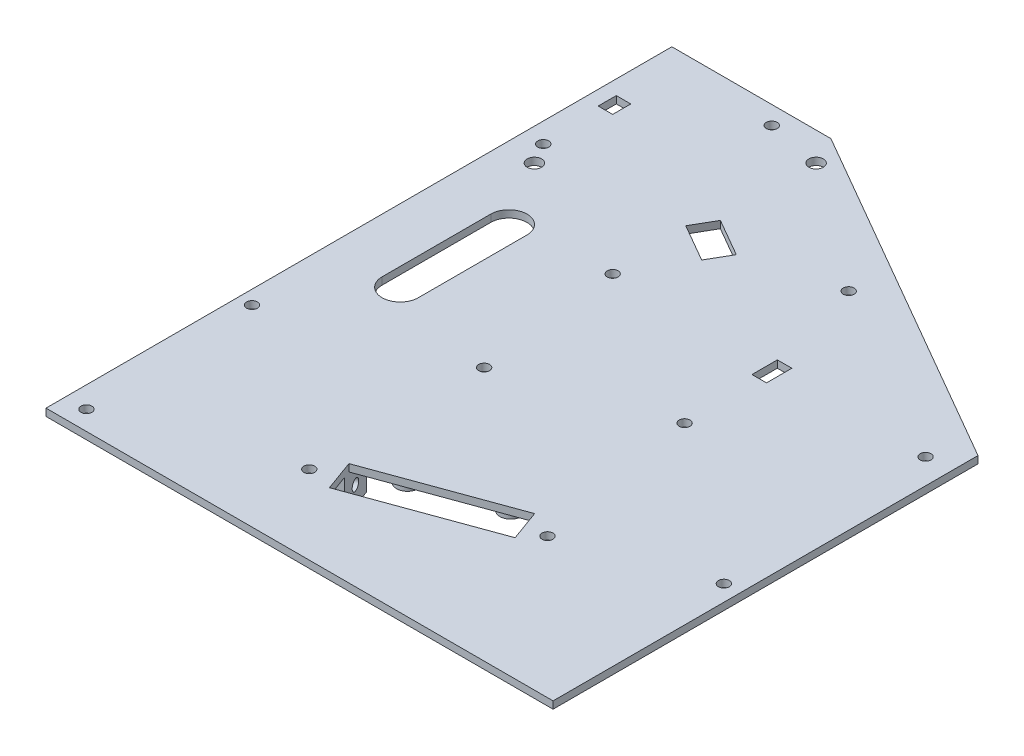
SolidWorks part; units mm, degrees
ref_plane "Front Plane" through (0, 0, 0) normal (0, 0, 1) x (1, 0, 0)
ref_plane "Top Plane" through (0, 0, 0) normal (0, 1, 0) x (1, 0, 0)
ref_plane "Right Plane" through (0, 0, 0) normal (1, 0, 0) x (0, 0, -1)
sketch "Sketch1" plane through (0, 0, 0) normal (0, 1, 0) x (1, 0, 0)
  line L1 (-70, 100) -> (70, 100)
  line L2 (-70, 100) -> (-70, -100)
  line L3 (-70, -100) -> (70, -100)
  line L4 (70, 100) -> (70, -100)
  line L5 (-70, 100) -> (70, -100) construction
  line L6 (-70, -100) -> (70, 100) construction
  point P0 (0, 0)
  dimension "D1" = 200
  dimension "D2" = 140
extrude "Boss-Extrude1" add sketch "Sketch1" along normal blind 2
sketch "Sketch2" plane through (0, 2, 0) normal (0, 1, 0) x (1, 0, 0)
  line L0 (-60, 63) -> (30, 11.0385) construction
  line L1 (-70, 100) -> (-70, -100) construction
  line L2 (70, -14.4027) -> (23.0154, -31.5037) construction
  line L3 (70, -100) -> (70, 100) construction
  line L4 (-50.6218, 98) -> (-70, 98) construction
  line L5 (-60, 63) -> (-50.6218, 63) construction
  line L6 (70, 100) -> (-70, 100) construction
  line L7 (70, -14.4027) -> (47.7176, -14.4027) construction
  line L8 (-51.25, 78.1554) -> (38.75, 26.1939) construction
  line L9 (-60, 63) -> (-70, 63) construction
  line L10 (-50.6218, 98) -> (70, 28.359) construction
  line L11 (-25.2872, 59.1244) -> (-21.7872, 65.1865)
  line L12 (-25.2872, 59.1244) -> (-14.8949, 53.1244)
  line L13 (-21.7872, 65.1865) -> (-11.3949, 59.1865)
  line L14 (-14.8949, 53.1244) -> (-11.3949, 59.1865)
  line L15 (-25.2872, 59.1244) -> (-11.3949, 59.1865)
  line L16 (-51.25, 78.1554) -> (-70, 78.1554) construction
  line L17 (-50.6218, 98) -> (47.5, 41.3494) construction
  line L18 (-66, 80.6554) -> (-62, 80.6554)
  line L19 (-66, 80.6554) -> (-66, 75.6554)
  line L20 (-66, 75.6554) -> (-62, 75.6554)
  line L21 (-62, 80.6554) -> (-62, 75.6554)
  line L22 (-66, 80.6554) -> (-62, 75.6554) construction
  line L23 (-66, 75.6554) -> (-62, 80.6554) construction
  line L24 (19.4272, 32.69) -> (23.4317, 32.69)
  line L25 (19.4272, 32.69) -> (19.4272, 39.6978)
  line L26 (19.4272, 39.6978) -> (23.4317, 39.6978)
  line L27 (23.4317, 32.69) -> (23.4317, 39.6978)
  line L28 (19.4272, 32.69) -> (23.4317, 39.6978) construction
  line L29 (19.4272, 39.6978) -> (23.4317, 32.69) construction
  line L30 (30, 11.0385) -> (30, -28.9615) construction
  line L31 (-70, -65.3585) -> (-14.5723, -45.1845) construction
  line L32 (30, 11.0385) -> (-70, -25.3585) construction
  circle A0 centre (-41.7237, 72.6554) radius 20
  point P10 (-18.341, 59.1554)
  point P13 (-64, 78.1554)
  point P25 (-64, 75.6554)
  point P26 (21.4295, 36.1939)
  dimension "D6" = 40
  dimension "D1" = 37
  dimension "D2" = 30
  dimension "D3" = 20
  dimension "D4" = 40
  dimension "D5" = 10
  dimension "D9" = 11
  dimension "D10" = 5
  dimension "D11" = 4
  dimension "D12" = 4
  dimension "D13" = 12
  dimension "D14" = 7
  dimension "D15" = 20
  dimension "D16" = 40
  dimension "D17" = 50
  dimension "D18" = 40
  dimension "D19" = 21
  dimension "D7" = 35
  dimension "D8" = 17.5
sketch "Sketch3" plane through (0, 2, 0) normal (0, 1, 0) x (1, 0, 0)
  line L0 (-50.6218, 98) -> (70, 28.359) construction
  line L1 (-60, 63) -> (30, 11.0385) construction
  line L2 (30, 11.0385) -> (-70, -25.3585) construction
  line L3 (70, -14.4027) -> (23.0154, -31.5037) construction
  line L4 (-70, -65.3585) -> (-14.5723, -45.1845) construction
  line L5 (-50.6218, 98) -> (70, 28.359)
  line L6 (-60, 63) -> (30, 11.0385)
  line L7 (30, 11.0385) -> (-70, -25.3585)
  line L8 (70, -14.4027) -> (23.0154, -31.5037)
  line L9 (-70, -65.3585) -> (-14.5723, -45.1845)
  line L10 (-60, 63) -> (-70, 63) construction
  line L11 (-60, 63) -> (-70, 63)
extrude "Cut-Extrude-Thin1" [suppressed] cut sketch "Sketch3" against normal blind 0.5 thin contours L11 L6 L7 thin type one direction wall 2.5
sketch "Sketch4" plane through (0, 0, 0) normal (0, -1, 0) x (1, 0, 0)
  circle A0 centre (-41.7237, -72.6554) radius 20 construction
  circle A1 centre (-41.7237, -72.6554) radius 20
extrude "Cut-Extrude1" cut sketch "Sketch4" against normal blind 1
sketch "Sketch6" plane through (0, 0, 0) normal (0, -1, 0) x (1, 0, 0)
  line L0 (-22.2783, -92.1009) -> (-61.1692, -53.21) construction
  line L1 (-23.6925, -93.5151) -> (-62.5834, -54.6242) construction
  line L2 (-20.8641, -90.6867) -> (-59.7549, -51.7958) construction
  line L4 (-51.25, -78.1554) -> (38.75, -26.1939) construction
  arc A0 (-23.6925, -93.5151) -> (-20.8641, -90.6867) centre (-22.2783, -92.1009) ccw construction
  arc A1 (-59.7549, -51.7958) -> (-62.5834, -54.6242) centre (-61.1692, -53.21) ccw construction
  circle A2 centre (-61.1692, -53.21) radius 2
  circle A3 centre (-22.2783, -92.1009) radius 2
  point P2 (-41.7237, -72.6554)
  dimension "D1" = 55
  dimension "D2" = 4
  dimension "D3" = 105
extrude "Cut-Extrude2" cut sketch "Sketch6" against normal up to next
extrude "Cut-Extrude4" cut sketch "Sketch2" against normal through all and the other way through all contours L15 L12 L14 | L11 L15 L13 | L21 L18 L19 L20 | L24 L27 L26 L25 region at (-17.1923, 2, -57.1451) region at (-19.4898, 2, -61.1658) region at (-64, 2, -78.1554) region at (21.4295, 2, -36.1939)
sketch "Sketch7" plane through (0, 2, 0) normal (0, 1, 0) x (1, 0, 0)
  line L0 (-14.5723, -45.1845) -> (23.0154, -31.5037)
  line L1 (23.0154, -31.5037) -> (25.7515, -39.0213)
  line L2 (25.7515, -39.0213) -> (-11.8362, -52.7021)
  line L3 (-11.8362, -52.7021) -> (-14.5723, -45.1845)
  line L4 (-14.5723, -45.1845) -> (23.0154, -31.5037)
  line L5 (-14.5723, -45.1845) -> (-14.9144, -44.2448)
  line L6 (23.0154, -31.5037) -> (22.6733, -30.564)
  line L7 (-14.9144, -44.2448) -> (22.6733, -30.564)
  line L8 (70, -14.4027) -> (23.0154, -31.5037) construction
  dimension "D1" = 8
  dimension "D2" = 40
  dimension "D3" = 1
extrude "Cut-Extrude5" cut sketch "Sketch7" against normal up to surface (2 mm away) contours L3 L2 L1 L0 | L7 L5 L0 L6 region at (4.0505, 2, 37.8743) region at (5.5896, 2, 42.1029) up to face at (21.4295, 0, -36.1939)
sketch "Sketch8" plane through (10.198, 0, -3.7118) normal (-0.9397, 0, 0.342) x (0.342, 0, 0.9397)
  line L1 (38.4755, 0) -> (28.4755, 0)
  line L2 (38.4755, 0) -> (38.4755, -10)
  line L3 (38.4755, -10) -> (28.4755, -10)
  line L4 (28.4755, 0) -> (28.4755, -10)
  line L5 (-96.9966, 0) -> (-92.2981, 0) construction
  circle A0 centre (33.4755, -5) radius 1.5
  point P9 (28.4755, -5)
  point P11 (33.4755, -10)
  dimension "D3" = 3
  dimension "D1" = 10
  dimension "D2" = 10
  dimension "D4" = 2
extrude "Boss-Extrude2" add sketch "Sketch8" against normal blind 4
ref_plane "Plane1" through (-8.5959, 0, 3.1286) normal (-0.9397, 0, 0.342) x (0.342, 0, 0.9397)
mirror "Mirror1" about plane through (-8.5959, 0, 3.1286) normal (-0.9397, 0, 0.342) of "Boss-Extrude2"
sketch "Sketch9" plane through (0, 0, 0) normal (0, -1, 0) x (-1, 0, 0)
  line L5 (15.4671, -16.7774) -> (9.3107, -33.6919) construction
  line L6 (16.4068, -17.1194) -> (10.2504, -34.0339)
  line L7 (14.5274, -16.4354) -> (8.3711, -33.3498)
  line L8 (-22.6733, -30.564) -> (14.9144, -44.2448) construction
  line L9 (17.6505, -36.7273) -> (14.2303, -46.1242) construction
  line L10 (18.2862, -17.8035) -> (12.1298, -34.7179)
  line L11 (12.648, -15.7513) -> (6.4917, -32.6658)
  arc A0 (16.4068, -17.1194) -> (14.5274, -16.4354) centre (15.4671, -16.7774) ccw
  arc A1 (8.3711, -33.3498) -> (10.2504, -34.0339) centre (9.3107, -33.6919) ccw
  arc A2 (6.4917, -32.6658) -> (12.1298, -34.7179) centre (9.3107, -33.6919) ccw
  arc A3 (18.2862, -17.8035) -> (12.648, -15.7513) centre (15.4671, -16.7774) ccw
  point P7 (12.3889, -25.2346)
  dimension "D5" = 1
  dimension "D1" = 8
  dimension "D2" = 7.875
  dimension "D3" = 2
  dimension "D7" = 18
extrude "Boss-Extrude4" add sketch "Sketch9" along normal blind 5
mirror "Mirror2" about plane through (-8.5959, 0, 3.1286) normal (-0.9397, 0, 0.342) of "Boss-Extrude4"
sketch "Sketch10" plane through (0, 0, 0) normal (0, -1, 0) x (1, 0, 0)
  line L0 (-28.8362, -55.9772) -> (-26.2381, -54.4772)
  line L1 (-28.8362, -55.9772) -> (-31.5862, -51.2141)
  line L2 (-26.2381, -54.4772) -> (-28.9881, -49.7141)
  line L3 (-31.5862, -51.2141) -> (-28.9881, -49.7141)
  line L4 (-25.2872, -59.1244) -> (-14.8949, -53.1244) construction
  line L6 (-25.2872, -59.1244) -> (-21.7872, -65.1865) construction
  dimension "D1" = 4.5
  dimension "D2" = 5.5
  dimension "D3" = 3
  dimension "D4" = 1.5
extrude "Boss-Extrude5" add sketch "Sketch10" along normal blind 23
sketch "Sketch11" plane through (-45.866, 0, -26.4808) normal (-0.866, 0, -0.5) x (-0.5, 0, 0.866)
  line L0 (-31.5596, -20.0043) -> (-31.5596, -16.0043) construction
  line L1 (-32.5596, -20.0043) -> (-32.5596, -16.0043)
  line L2 (-30.5596, -20.0043) -> (-30.5596, -16.0043)
  line L3 (-28.5596, -23) -> (-34.0596, -23) construction
  line L4 (-28.5596, -23) -> (-28.5596, 0) construction
  line L5 (-31.5596, -6.5043) -> (-31.5596, -2.5043) construction
  line L6 (-32.5596, -6.5043) -> (-32.5596, -2.5043)
  line L7 (-30.5596, -6.5043) -> (-30.5596, -2.5043)
  arc A0 (-32.5596, -20.0043) -> (-30.5596, -20.0043) centre (-31.5596, -20.0043) ccw
  arc A1 (-30.5596, -16.0043) -> (-32.5596, -16.0043) centre (-31.5596, -16.0043) ccw
  arc A2 (-32.5596, -6.5043) -> (-30.5596, -6.5043) centre (-31.5596, -6.5043) ccw
  arc A3 (-30.5596, -2.5043) -> (-32.5596, -2.5043) centre (-31.5596, -2.5043) ccw
  point P3 (-31.5596, -18.0043)
  point P19 (-31.5596, -4.5043)
  dimension "D1" = 2.9957
  dimension "D2" = 4
  dimension "D3" = 3
  dimension "D4" = 2
  dimension "D5" = 13.5
extrude "Cut-Extrude6" cut sketch "Sketch11" against normal up to next
ref_plane "Plane2" through (21.0298, 0, -36.4247) normal (-0.5, 0, 0.866) x (0.866, 0, 0.5)
mirror "Mirror3" about plane through (21.0298, 0, -36.4247) normal (-0.5, 0, 0.866) of "Cut-Extrude6", "Boss-Extrude5"
hole_wizard "Ø3.0mm Clearance Dowel Hole1" positions "Sketch14" profile "Sketch15" hole size "Ø3.0" standard "ANSI Metric" end condition through all
sketch "Sketch14" plane through (-89.742, 2, 119.4997) normal (0, 1, 0) x (1, 0, 0)
  point P0 (23.5423, 99.781)
  point P1 (25.5944, 52.0145)
  point P2 (70.6996, 68.4315)
  point P3 (70.5269, 116.8821)
  point P4 (111.4918, 131.26)
  point P5 (119.5864, 85.3143)
  point P6 (155.2948, 98.311)
  point P7 (152.8064, 156.4818)
  point P8 (65.8782, 157.0177)
  point P9 (102.577, 185.4818)
  point P10 (52.3475, 214.4818)
  point P11 (25.242, 178.4997)
sketch "Sketch15" plane through (-66.1998, 2, 19.7187) normal (1, 0, 0) x (0, 0, 1)
  line L0 (0, 0) -> (0, 25)
  line L1 (0, 25) -> (1.5, 25)
  line L2 (1.5, 25) -> (1.5, 0)
  line L3 (1.5, 0) -> (0, 0)
  line L4 (0, -6.35) -> (0, 107.95) construction
  dimension "Thru Hole Dia." = 3
  dimension "Thru Hole Depth" = 25
sketch "Sketch16" plane through (0, 2, 0) normal (0, 1, 0) x (1, 0, 0)
  line L1 (-43.6218, 110.1244) -> (83.0261, 110.1244)
  line L2 (-43.6218, 110.1244) -> (77, 40.4833)
  line L3 (-43.6218, 110.1244) -> (77, 40.4833)
  line L4 (83.0261, 110.1244) -> (83.0261, 36.9032)
  line L5 (83.0261, 36.9032) -> (77, 40.4833)
  dimension "D1" = 14
extrude "Cut-Extrude7" cut sketch "Sketch16" against normal through all
sketch "Sketch17" plane through (0, 2, 0) normal (0, 1, 0) x (1, 0, 0)
  line L0 (-43.2303, 98) -> (-26.6218, 98)
  line L1 (-26.6218, 98) -> (68, 43.3701)
  line L2 (68, 43.3701) -> (68, 33.0364)
  line L3 (70, -100) -> (70, 44.5248) construction
  line L4 (-26.0859, 100) -> (70, 44.5248) construction
  line L5 (-26.0859, 100) -> (-70, 100) construction
  line L6 (-43.2303, 98) -> (-46.6944, 100)
  line L7 (-46.6944, 100) -> (-26.0859, 100)
  line L8 (-26.0859, 100) -> (70, 44.5248)
  line L9 (70, 44.5248) -> (70, 31.875)
  line L10 (70, 31.875) -> (68, 33.0364)
  dimension "D1" = 2
  dimension "D2" = 2
  dimension "D3" = 2
extrude "Boss-Extrude6" [suppressed] add sketch "Sketch17" along normal blind 4
sketch "Sketch18" plane through (0, 2, 0) normal (0, 1, 0) x (1, 0, 0)
  line L0 (-70, 100) -> (-70, -100) construction
  line L1 (-70, -72.7995) -> (70, -72.7995)
  line L2 (-70, -72.7995) -> (-70, -100)
  line L3 (-70, -100) -> (70, -100)
  line L4 (70, -72.7995) -> (70, -100)
extrude "Cut-Extrude8" cut sketch "Sketch18" against normal through all
extrude "Cut-Extrude9" cut sketch "Sketch19" against normal through all
sketch "Sketch19" plane through (-89.742, 8, 119.4997) normal (0, 1, 0) x (1, 0, 0)
  line L0 (39.742, 154.4997) -> (39.742, 124.4997) construction
  line L1 (44.742, 154.4997) -> (44.742, 124.4997)
  line L2 (34.742, 154.4997) -> (34.742, 124.4997)
  arc A0 (44.742, 154.4997) -> (34.742, 154.4997) centre (39.742, 154.4997) ccw
  arc A1 (34.742, 124.4997) -> (44.742, 124.4997) centre (39.742, 124.4997) ccw
  point P2 (39.742, 139.4997)
  point P9 (0, 0)
